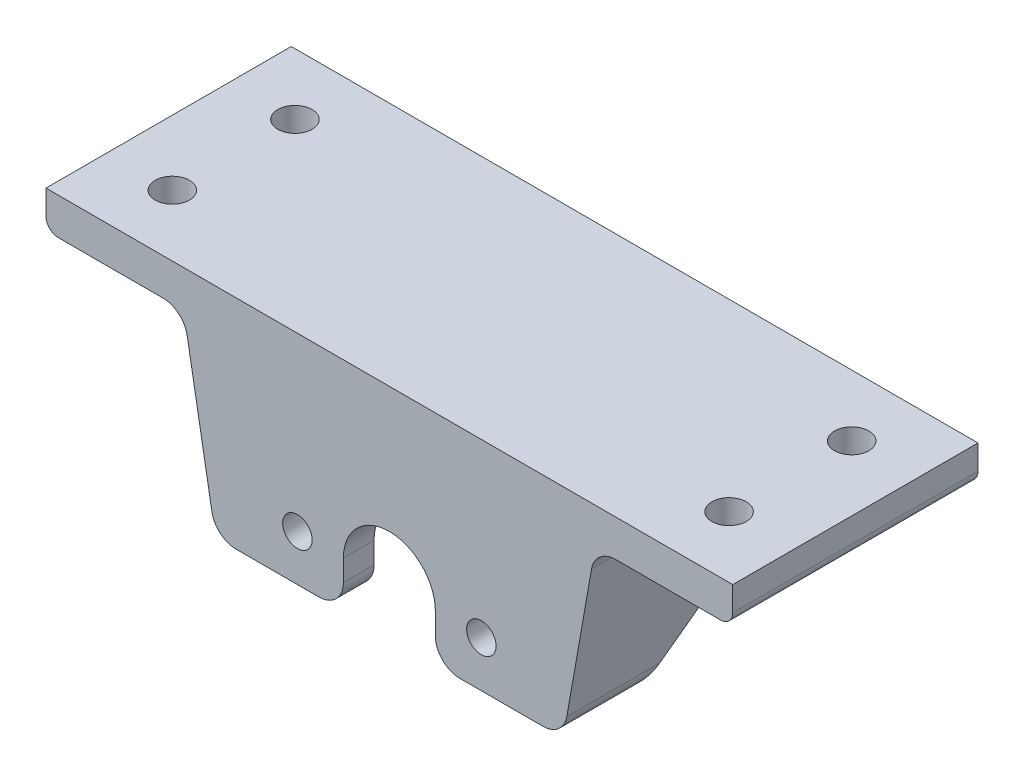
SolidWorks part; units mm, degrees
ref_plane "Front Plane" through (0, 0, 0) normal (0, 0, 1) x (1, 0, 0)
ref_plane "Top Plane" through (0, 0, 0) normal (0, 1, 0) x (1, 0, 0)
ref_plane "Right Plane" through (0, 0, 0) normal (1, 0, 0) x (0, 0, -1)
sketch "Motor Profile" plane through (0, 0, 0) normal (0, 0, 1) x (1, 0, 0)
  circle A0 centre (0, 0) radius 10 construction
  circle A1 centre (-7.5, 0) radius 1 construction
  circle A2 centre (7.5, 0) radius 1 construction
  circle A3 centre (0, 0) radius 3.5 construction
  dimension "D1" = 7
  dimension "D2" = 2
  dimension "D3" = 20
  dimension "D4" = 2
  dimension "D5" = 15
  dimension "D6" = 7.5
sketch "Sketch2" plane through (0, 0, 0) normal (0, 0, 1) x (1, 0, 0)
  line L0 (-3.75, 0) -> (-3.75, -1.75)
  line L1 (3.75, 0) -> (3.75, -1.75)
  line L2 (-5.75, -3.75) -> (-12.5, -3.75)
  line L3 (-14.4696, -2.0973) -> (-16.4876, 9.3473)
  line L4 (5.75, -3.75) -> (12.5, -3.75)
  line L5 (14.4696, -2.0973) -> (16.4876, 9.3473)
  line L7 (-18.4572, 11) -> (-27, 11)
  line L8 (18.4572, 11) -> (27, 11)
  line L9 (-28, 12) -> (-28, 14)
  line L10 (-28, 14) -> (28, 14)
  line L11 (28, 14) -> (28, 12)
  arc A0 (3.75, 0) -> (-3.75, 0) centre (0, 0) ccw
  circle A1 centre (-7.5, 0) radius 1.2
  circle A2 centre (7.5, 0) radius 1.2
  arc A3 (-5.75, -3.75) -> (-3.75, -1.75) centre (-5.75, -1.75) ccw
  arc A4 (5.75, -3.75) -> (3.75, -1.75) centre (5.75, -1.75) cw
  arc A5 (-12.5, -3.75) -> (-14.4696, -2.0973) centre (-12.5, -1.75) cw
  arc A6 (14.4696, -2.0973) -> (12.5, -3.75) centre (12.5, -1.75) cw
  arc A8 (-16.4876, 9.3473) -> (-18.4572, 11) centre (-18.4572, 9) ccw
  arc A9 (16.4876, 9.3473) -> (18.4572, 11) centre (18.4572, 9) cw
  arc A10 (-27, 11) -> (-28, 12) centre (-27, 12) cw
  arc A11 (28, 12) -> (27, 11) centre (27, 12) cw
  point P20 (-3.75, -3.75)
  point P23 (3.75, -3.75)
  point P27 (-14.1782, -3.75)
  point P33 (-16.779, 11)
  point P36 (16.779, 11)
  point P39 (-28, 11)
  dimension "D1" = 7.5
  dimension "D2" = 2.4
  dimension "D7" = 2
  dimension "D8" = 2
  dimension "D9" = 2
  dimension "D10" = 2
  dimension "D13" = 2
  dimension "D14" = 2
  dimension "D16" = 1
  dimension "D17" = 1
  dimension "D4" = 3.75
  dimension "D3" = 80
  dimension "D5" = 80
  dimension "D6" = 5
  dimension "D11" = 11
  dimension "D12" = 3
  dimension "D15" = 56
extrude "Boss-Extrude1" add sketch "Sketch2" against normal blind 2.5
ref_plane "Plane2" through (0, 0, -20) normal (0, 0, 1) x (1, 0, 0)
sketch "Sketch3" plane through (0, 0, -2.5) normal (0, 0, -1) x (-1, 0, 0)
  line L11 (-11, -2.75) -> (-11, 6)
  line L12 (-5.75, -3.75) -> (-12.5, -3.75) construction
  line L13 (-6, 11) -> (6, 11)
  line L14 (11, 6) -> (11, -2.75)
  line L15 (12.5, -3.75) -> (5.75, -3.75) construction
  line L16 (12, -3.75) -> (12.5, -3.75)
  line L17 (-12, -3.75) -> (-12.5, -3.75)
  line L22 (3.75, 0) -> (3.75, -1.75)
  line L23 (5.75, -3.75) -> (12.5, -3.75)
  line L24 (14.4696, -2.0973) -> (16.4876, 9.3473)
  line L25 (18.4572, 11) -> (27, 11)
  line L26 (28, 12) -> (28, 14)
  line L27 (28, 14) -> (-28, 14)
  line L28 (-28, 14) -> (-28, 12)
  line L29 (-27, 11) -> (-18.4572, 11)
  line L30 (-16.4876, 9.3473) -> (-14.4696, -2.0973)
  line L31 (-12.5, -3.75) -> (-5.75, -3.75)
  line L32 (-3.75, -1.75) -> (-3.75, 0)
  line L35 (14.4696, -2.0973) -> (16.4876, 9.3473)
  line L36 (18.4572, 11) -> (27, 11)
  line L37 (28, 12) -> (28, 14)
  line L38 (28, 14) -> (-28, 14)
  line L39 (-28, 14) -> (-28, 12)
  line L40 (-27, 11) -> (-18.4572, 11)
  line L41 (-16.4876, 9.3473) -> (-14.4696, -2.0973)
  arc A9 (-11, 6) -> (-6, 11) centre (-6, 6) cw
  arc A10 (11, 6) -> (6, 11) centre (6, 6) ccw
  arc A11 (-11, -2.75) -> (-12, -3.75) centre (-12, -2.75) cw
  arc A12 (12, -3.75) -> (11, -2.75) centre (12, -2.75) cw
  arc A18 (3.75, 0) -> (-3.75, 0) centre (0, 0) ccw
  arc A19 (3.75, -1.75) -> (5.75, -3.75) centre (5.75, -1.75) ccw
  arc A20 (12.5, -3.75) -> (14.4696, -2.0973) centre (12.5, -1.75) ccw
  arc A21 (18.4572, 11) -> (16.4876, 9.3473) centre (18.4572, 9) ccw
  arc A22 (27, 11) -> (28, 12) centre (27, 12) ccw
  arc A23 (-28, 12) -> (-27, 11) centre (-27, 12) ccw
  arc A24 (-16.4876, 9.3473) -> (-18.4572, 11) centre (-18.4572, 9) ccw
  arc A25 (-14.4696, -2.0973) -> (-12.5, -3.75) centre (-12.5, -1.75) ccw
  arc A26 (-5.75, -3.75) -> (-3.75, -1.75) centre (-5.75, -1.75) ccw
  arc A29 (12.5, -3.75) -> (14.4696, -2.0973) centre (12.5, -1.75) ccw
  arc A30 (18.4572, 11) -> (16.4876, 9.3473) centre (18.4572, 9) ccw
  arc A31 (27, 11) -> (28, 12) centre (27, 12) ccw
  arc A32 (-28, 12) -> (-27, 11) centre (-27, 12) ccw
  arc A33 (-16.4876, 9.3473) -> (-18.4572, 11) centre (-18.4572, 9) ccw
  arc A34 (-14.4696, -2.0973) -> (-12.5, -3.75) centre (-12.5, -1.75) ccw
  point P7 (0, 11)
  point P26 (-11, -3.75)
  point P29 (11, -3.75)
  dimension "D3" = 5
  dimension "D4" = 5
  dimension "D5" = 1
  dimension "D6" = 1
  dimension "D2" = 11
  dimension "D1" = 0
extrude "Boss-Extrude2" add sketch "Sketch3" along direction (0, 0, 1) on the side of the normal up to surface (17.5 mm away) up to plane "Plane2"
sketch "Sketch6" plane through (0, 0, 0) normal (1, 0, 0) x (0, 0, -1)
  line L0 (6, -3.75) -> (20, 11)
  line L1 (20, -3.75) -> (0, -3.75) construction
  line L2 (20, 9.7625) -> (20, -9.7625) construction
  line L3 (20, 11) -> (0, 11) construction
  line L4 (6, -3.75) -> (20, -3.75)
  line L5 (20, -3.75) -> (20, 11)
  dimension "D1" = 6
extrude "Cut-Extrude1" cut sketch "Sketch6" against normal through all both and the other way through all
sketch "Sketch9" plane through (0, 11, 0) normal (0, -1, 0) x (1, 0, 0)
  line L0 (18.4572, -20) -> (27, -20) construction
  line L1 (28, -20) -> (28, 0) construction
  line L3 (18.4572, 0) -> (27, 0) construction
  circle A0 centre (22.7, -15) radius 1.4
  circle A1 centre (22.7, -5) radius 1.4
  dimension "D1" = 2.8
  dimension "D2" = 5
  dimension "D3" = 5
  dimension "D4" = 5.3
extrude "Cut-Extrude2" cut sketch "Sketch9" against normal through all
mirror "Mirror1" about plane through (0, 0, 0) normal (1, 0, 0) of "Cut-Extrude2"
equation "\"D6@Motor Profile\" = \"D5@Motor Profile\" / 2"
equation "\"D5@Sketch2\"=\"D3@Sketch2\""
